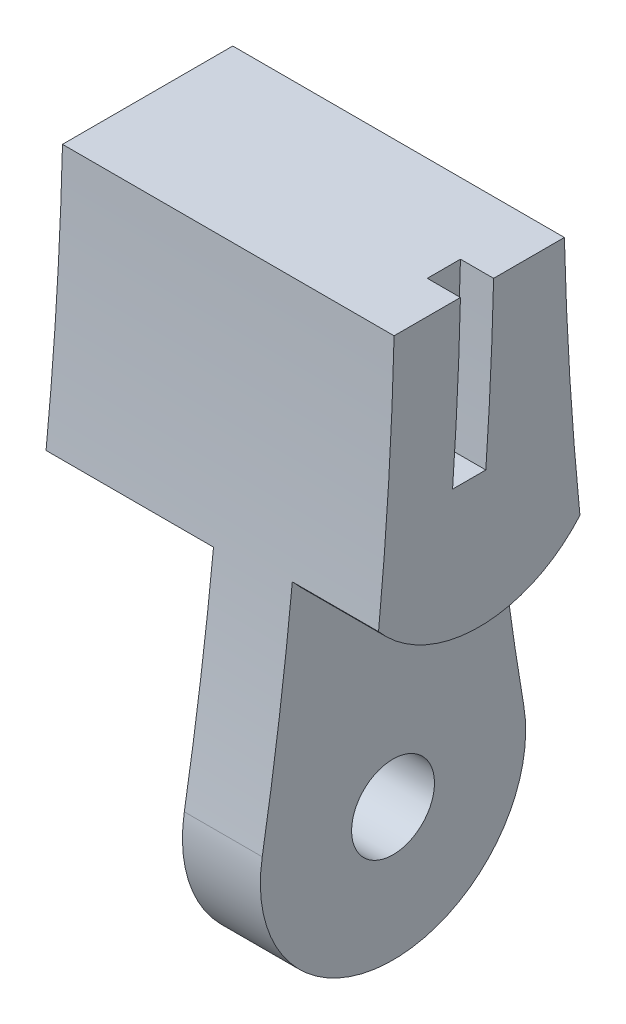
SolidWorks part; units mm, degrees
ref_plane "Front Plane" through (0, 0, 0) normal (0, 0, 1) x (1, 0, 0)
ref_plane "Top Plane" through (0, 0, 0) normal (0, 1, 0) x (1, 0, 0)
ref_plane "Right Plane" through (0, 0, 0) normal (1, 0, 0) x (0, 0, -1)
sketch "Sketch1" plane through (0, 0, 0) normal (1, 0, 0) x (0, 0, -1)
  arc A0 (9.7654, 20.1165) -> (-9.7654, 20.1165) centre (0, 22.2701) ccw
  arc A1 (-7.8874, -56.3924) -> (7.8874, -56.3924) centre (0, -57.7299) ccw
  arc A2 (-7.8874, -56.3924) -> (-9.7654, 20.1165) centre (-205.0724, -22.9549) ccw
  circle A3 centre (0, 22.2701) radius 1.5
  arc A4 (9.7654, 20.1165) -> (7.8874, -56.3924) centre (205.0724, -22.9549) ccw
  circle A5 centre (0, -57.7299) radius 2.5
extrude "Boss-Extrude1" add sketch "Sketch1" along normal blind 20
sketch "Sketch2" plane through (0, 0, 0) normal (0, 0, 1) x (1, 0, 0)
  line L1 (0, -65.7299) -> (8.1, -65.7299)
  line L2 (0, -65.7299) -> (0, -45.7299)
  line L3 (0, -45.7299) -> (8.1, -45.7299)
  line L4 (8.1, -65.7299) -> (8.1, -45.7299)
  line L5 (20, -65.7299) -> (14.8, -65.7299)
  line L6 (20, -65.7299) -> (20, -45.7299)
  line L7 (20, -45.7299) -> (14.8, -45.7299)
  line L8 (14.8, -65.7299) -> (14.8, -45.7299)
  line L11 (3, 32.2701) -> (8.1, 32.2701)
  line L12 (3, 32.2701) -> (3, 12.2701)
  line L13 (3, 12.2701) -> (8.1, 12.2701)
  line L14 (8.1, 32.2701) -> (8.1, 12.2701)
extrude "Cut-Extrude1" cut sketch "Sketch2" against normal blind 20 and the other way blind 20
sketch "Sketch3" plane through (8.1, 0, 0) normal (-1, 0, 0) x (0, 0, 1)
  line L0 (8.5, 22.2701) -> (8.5, 40.9095)
  line L1 (8.5, 40.9095) -> (-17.5287, 40.9095)
  line L2 (-17.5287, 40.9095) -> (-17.5287, 13.7701)
  line L3 (0, 13.7701) -> (-17.5287, 13.7701)
  arc A0 (0, 13.7701) -> (8.5, 22.2701) centre (0, 22.2701) ccw
extrude "Cut-Extrude2" cut sketch "Sketch3" against normal blind 9
sketch "Sketch4" plane through (8.1, 0, 0) normal (-1, 0, 0) x (0, 0, 1)
  line L0 (8.5, 27.5379) -> (8.2838, 12.7416)
  line L1 (8.2838, 12.7416) -> (10.2838, 12.7416)
  line L2 (10.2838, 12.7416) -> (10.2838, 27.5379)
  line L3 (10.2838, 27.5379) -> (8.5, 27.5379)
  arc A0 (9.7654, 20.1165) -> (6.3734, -45.7299) centre (205.0724, -22.9549) ccw construction
extrude "Boss-Extrude2" add sketch "Sketch4" against normal through all
sketch "Sketch5" plane through (8.1, 0, 0) normal (-1, 0, 0) x (0, 0, 1)
  line L4 (8.1452, 11.9686) -> (8.4478, 23.9686)
  line L6 (15.0224, 23.9686) -> (9.8547, 23.9686)
  line L8 (8.1452, 11.9686) -> (15.0224, 11.9686)
  line L9 (8.5, 27.5379) -> (8.4045, 20.9993) construction
  line L10 (8.4478, 23.9686) -> (9.8547, 23.9686)
  circle A2 centre (15.0224, 17.9686) radius 3
  arc A5 (15.0224, 11.9686) -> (15.0224, 23.9686) centre (15.0224, 17.9686) ccw
  arc A6 (9.7654, 20.1165) -> (-9.7654, 20.1165) centre (0, 22.2701) ccw construction
  arc A7 (9.7654, 20.1165) -> (6.3734, -45.7299) centre (205.0724, -22.9549) ccw construction
extrude "Boss-Extrude3" add sketch "Sketch5" against normal blind 5
sketch "Sketch12" plane through (13.1, 0, 0) normal (1, 0, 0) x (0, 0, -1)
  line L2 (-13.9029, 14.9686) -> (-13.9029, 12.9686)
  line L4 (-15.9029, 14.9686) -> (-15.9029, 15.2943)
  line L5 (-15.9029, 15.2943) -> (-13.9029, 15.2943)
  line L6 (-13.9029, 12.9686) -> (-15.9029, 12.9686)
  line L7 (-13.9029, 14.9686) -> (-13.9029, 15.2943)
  line L11 (-15.9029, 14.9686) -> (-15.9029, 12.9686)
extrude "Cut-Extrude6" cut sketch "Sketch12" against normal blind 1
sketch "Sketch13" plane through (17.1, 0, 0) normal (-1, 0, 0) x (0, 0, 1)
  circle A0 centre (0, 22.2701) radius 2.5
extrude "Cut-Extrude7" cut sketch "Sketch13" against normal blind 4
sketch "Sketch15" plane through (0, 0, 0) normal (-1, 0, 0) x (0, 0, 1)
  line L0 (10, 22.2701) -> (10, 11.9686)
  line L1 (8.1452, 11.9686) -> (15.0224, 11.9686) construction
  line L2 (10, 11.9686) -> (8.1452, 11.9686)
  line L3 (10, 22.2701) -> (7.5957, 11.9686)
  line L4 (7.5957, 11.9686) -> (8.1452, 11.9686)
  arc A0 (9.7654, 20.1165) -> (-9.7654, 20.1165) centre (0, 22.2701) ccw construction
extrude "Boss-Extrude4" add sketch "Sketch15" against normal blind 3
sketch "Sketch16" plane through (20, 0, 0) normal (1, 0, 0) x (0, 0, -1)
  line L0 (-10.2838, 23.9686) -> (-9.8547, 23.9686)
  line L1 (-10.2838, 23.9686) -> (-10.2838, 27.5379)
  line L2 (-10.2838, 27.5379) -> (-8.5, 27.5379) construction
  line L3 (-10.2838, 12.7416) -> (-10.2838, 27.5379) construction
  line L4 (-10.2838, 27.5379) -> (-8.5, 27.5379)
  arc A0 (-8.5, 27.5379) -> (-9.8547, 23.9686) centre (0, 22.2701) ccw
extrude "Cut-Extrude9" cut sketch "Sketch16" against normal blind 3
sketch "Sketch17" plane through (0, 0, 10.2838) normal (0, 0, 1) x (1, 0, 0)
  line L1 (17.1, 27.5379) -> (8.1, 27.5379)
  line L2 (17.1, 27.5379) -> (17.1, 23.9686)
  line L3 (17.1, 23.9686) -> (8.1, 23.9686)
  line L4 (8.1, 27.5379) -> (8.1, 23.9686)
extrude "Cut-Extrude11" cut sketch "Sketch17" against normal blind 3
sketch "Sketch18" plane through (13.1, 0, 0) normal (1, 0, 0) x (0, 0, -1)
  line L1 (-10.2838, 12.7416) -> (-4.5128, 12.7416)
  line L2 (-10.2838, 12.7416) -> (-10.2838, 11.9686)
  line L3 (-10.2838, 11.9686) -> (-4.5128, 11.9686)
  line L4 (-4.5128, 12.7416) -> (-4.5128, 11.9686)
extrude "Boss-Extrude5" add sketch "Sketch18" along normal through all and the other way blind 1
sketch "Sketch19" plane through (0, 12.2701, 0) normal (0, 1, 0) x (1, 0, 0)
  line L1 (8.1, -8.1989) -> (3, -8.1989)
  line L2 (8.1, -8.1989) -> (8.1, 8.1989)
  line L3 (8.1, 8.1989) -> (3, 8.1989)
  line L4 (3, -8.1989) -> (3, 8.1989)
extrude "Cut-Extrude12" cut sketch "Sketch19" against normal up to surface (0.3015 mm away) up to face at (1.5, 11.9686, 9.0726)
sketch "Sketch20" plane through (17.1, 0, 0) normal (-1, 0, 0) x (0, 0, 1)
  line L1 (2.5, 22.2701) -> (-2.5, 22.2701)
  line L2 (2.5, 22.2701) -> (2.5, 34.6894)
  line L3 (2.5, 34.6894) -> (-2.5, 34.6894)
  line L4 (-2.5, 22.2701) -> (-2.5, 34.6894)
  circle A0 centre (0, 22.2701) radius 2.5 construction
extrude "Cut-Extrude13" cut sketch "Sketch20" against normal blind 10
sketch "Sketch21" plane through (17.1, 0, 0) normal (-1, 0, 0) x (0, 0, 1)
  line L1 (-8.4732, 13.7701) -> (0.2785, 12.274)
  line L3 (2.5, 22.2701) -> (2.5, 31.9526)
  line L5 (-2.5, 22.2701) -> (-2.5, 31.9526)
  arc A0 (0.2785, 12.274) -> (2.5, 31.9526) centre (0, 22.2701) ccw
  arc A1 (-2.5, 22.2701) -> (2.5, 22.2701) centre (0, 22.2701) ccw
  arc A2 (-2.5, 31.9526) -> (-9.7654, 20.1165) centre (0, 22.2701) ccw
  arc A7 (-8.4732, 13.7701) -> (-9.7654, 20.1165) centre (-205.0724, -22.9549) ccw
extrude "Boss-Extrude6" add sketch "Sketch21" along normal blind 2
sketch "Sketch23" plane through (0, 0, 10.2838) normal (0, 0, 1) x (1, 0, 0)
  line L1 (15.1, 23.9686) -> (20, 23.9686)
  line L2 (15.1, 23.9686) -> (15.1, 29.9686)
  line L3 (15.1, 29.9686) -> (20, 29.9686)
  line L4 (20, 23.9686) -> (20, 29.9686)
extrude "Boss-Extrude7" add sketch "Sketch23" against normal blind 4
sketch "Sketch22" plane through (0, 0, 10.2838) normal (0, 0, 1) x (1, 0, 0)
  circle A1 centre (17.55, 26.8701) radius 1
extrude "Cut-Extrude15" cut sketch "Sketch22" against normal blind 8
sketch "Sketch24" plane through (8.1, 0, 0) normal (-1, 0, 0) x (0, 0, 1)
  line L0 (5.1478, 19.7374) -> (5.1478, 15.5063)
  line L2 (8.4478, 23.9686) -> (8.4478, 15.5063)
  line L3 (8.4478, 15.5063) -> (5.1478, 15.5063)
  arc A0 (0, 13.7701) -> (8.3673, 20.7738) centre (0, 22.2701) ccw construction
  ellipse E0 centre (8.4478, 19.7374) end of major axis (8.4478, 15.5063) minor radius 3.3 (8.4478, 23.9686) -> (5.1478, 19.7374) ccw
extrude "Boss-Extrude8" add sketch "Sketch24" against normal blind 2
sketch "Sketch14" plane through (0, 0, 0) normal (-1, 0, 0) x (0, 0, 1)
  circle A3 centre (7.5326, 18.3318) radius 1.5
extrude "Cut-Extrude8" cut sketch "Sketch14" against normal up to surface (10.1 mm away) up to face at (10.1, 20.14, 6.7306)
sketch "Sketch25" plane through (8.1, 0, 0) normal (-1, 0, 0) x (0, 0, 1)
  line L0 (12, -45.7299) -> (8.3462, -36.9607)
  line L1 (-12, -45.7299) -> (-12, -57.7299)
  line L2 (12, -45.7299) -> (12, -57.7299)
  line L3 (-12, -45.7299) -> (-8.3462, -36.9607)
  line L5 (2.5, -53.2274) -> (2.5, -45.7299)
  line L7 (-2.5, -53.2274) -> (-2.5, -45.7299)
  arc A0 (-2.5, -53.2274) -> (2.5, -53.2274) centre (0, -57.7299) ccw
  arc A1 (-12, -57.7299) -> (12, -57.7299) centre (0, -57.7299) ccw
  arc A2 (2.5, -45.7299) -> (8.3462, -36.9607) centre (0, -37.7299) ccw
  arc A4 (-8.3462, -36.9607) -> (-2.5, -45.7299) centre (0, -37.7299) ccw
extrude "Cut-Extrude17" cut sketch "Sketch25" against normal blind 2 and the other way up to surface (8.1 mm away) other way up to face at (0, 18.3318, 9.0326)
sketch "Sketch26" plane through (20, 0, 0) normal (1, 0, 0) x (0, 0, -1)
  line L0 (-10.2838, 11.9686) -> (-10.2838, 29.9686) construction
  line L1 (-7.21, 15.0854) -> (-10.2838, 15.0854)
  line L3 (-7.21, 17.0854) -> (-10.2838, 17.0854)
  line L4 (-10.2838, 15.0854) -> (-10.2838, 17.0854)
  line L8 (-1.6082, -37.73) -> (0.397, -37.73)
  arc A0 (-4.2066, 12.6671) -> (-7.21, 15.0854) centre (-7.21, 12.0113) ccw
  arc A1 (-2.2434, 13.0504) -> (-7.21, 17.0854) centre (-7.21, 12.0113) ccw
  arc A2 (-2.3994, -46.1854) -> (-4.2066, 12.6671) centre (-205.0724, -22.9549) ccw
  arc A3 (-1.6082, -37.73) -> (-4.2066, 12.6671) centre (-205.0724, -22.9549) ccw
  circle A4 centre (-7.21, 12.0113) radius 5.0741 construction
  circle A5 centre (-7.21, 12.0113) radius 3.0741 construction
  arc A6 (-0.4124, -46.4131) -> (-2.2373, 13.0163) centre (-205.0724, -22.9549) ccw
  arc A7 (0.397, -37.73) -> (-2.2434, 13.0504) centre (-205.0724, -22.9549) ccw
  dimension "D3" = 2
  dimension "D1" = 4
  dimension "D2" = 6
extrude "Cut-Extrude18" cut sketch "Sketch26" against normal blind 2
sketch "Sketch29" plane through (20, 0, 0) normal (1, 0, 0) x (0, 0, -1)
  line L1 (8, -37.7299) -> (8.1403, -37.7299)
  line L2 (-15.7549, -37.7299) -> (-8, -37.7299)
  line L3 (-15.7549, -37.7299) -> (-15.7549, -45.9375)
  line L4 (-15.7549, -45.9375) -> (8.1403, -45.9375)
  line L5 (8.1403, -37.7299) -> (8.1403, -45.9375)
  arc A0 (-8, -37.7299) -> (8, -37.7299) centre (0, -37.7299) ccw
extrude "Cut-Extrude20" cut sketch "Sketch29" against normal up to surface (5.2 mm away) up to face at (14.8, -57.7299, -2.5)
sketch "Sketch30" plane through (0, 0, 10.2838) normal (0, 0, 1) x (1, 0, 0)
  line L1 (13.1, 11.9686) -> (20, 11.9686)
  line L2 (13.1, 11.9686) -> (13.1, 31.9686)
  line L3 (13.1, 31.9686) -> (20, 31.9686)
  line L4 (20, 11.9686) -> (20, 31.9686)
extrude "Cut-Extrude21" cut sketch "Sketch30" against normal up to surface (0.2838 mm away) up to face at (1.5, 17.1194, 10)
sketch "Sketch31" plane through (0, 23.9686, 0) normal (0, 1, 0) x (1, 0, 0)
  line L0 (8.1, -15.0224) -> (8.1, -8.4478) construction
  line L1 (8.1, -10) -> (10.1, -10)
  line L2 (8.1, -10) -> (8.1, -21.0224)
  line L3 (8.1, -21.0224) -> (10.1, -21.0224)
  line L4 (10.1, -10) -> (10.1, -21.0224)
  line L5 (8.1, -21.0224) -> (13.1, -21.0224) construction
extrude "Cut-Extrude22" cut sketch "Sketch31" against normal up to next
sketch "Sketch32" plane through (8.1, 0, 0) normal (-1, 0, 0) x (0, 0, 1)
  line L0 (-8.4732, 13.7701) -> (-8.4732, 5.4011)
  line L2 (5.1478, 15.5063) -> (-8.4732, 5.4011)
  line L5 (5.1478, 15.5063) -> (-8.4732, 13.7701)
extrude "Cut-Extrude23" cut sketch "Sketch32" against normal blind 7
sketch "Sketch33" plane through (20, 0, 0) normal (1, 0, 0) x (0, 0, -1)
  line L2 (-9.3048, -22.9549) -> (-9.3048, -27.9549)
  line L3 (-9.3048, -27.9549) -> (8.8924, -27.9549)
  line L4 (8.8924, -22.9549) -> (8.8924, -27.9549)
  line L6 (-9.3048, -22.9549) -> (-9.3048, -17.9549)
  line L7 (-9.3048, -17.9549) -> (8.8924, -17.9549)
  line L8 (8.8924, -22.9549) -> (8.8924, -17.9549)
extrude "Cut-Extrude24" cut sketch "Sketch33" against normal through all
sketch "Sketch34" plane through (20, 0, 0) normal (1, 0, 0) x (0, 0, -1)
  line L1 (-39.9209, -19.7225) -> (30.7316, -19.7225)
  line L2 (-39.9209, -19.7225) -> (-39.9209, 54.6123)
  line L3 (-39.9209, 54.6123) -> (30.7316, 54.6123)
  line L4 (30.7316, -19.7225) -> (30.7316, 54.6123)
extrude "Cut-Extrude25" cut sketch "Sketch34" against normal through all
